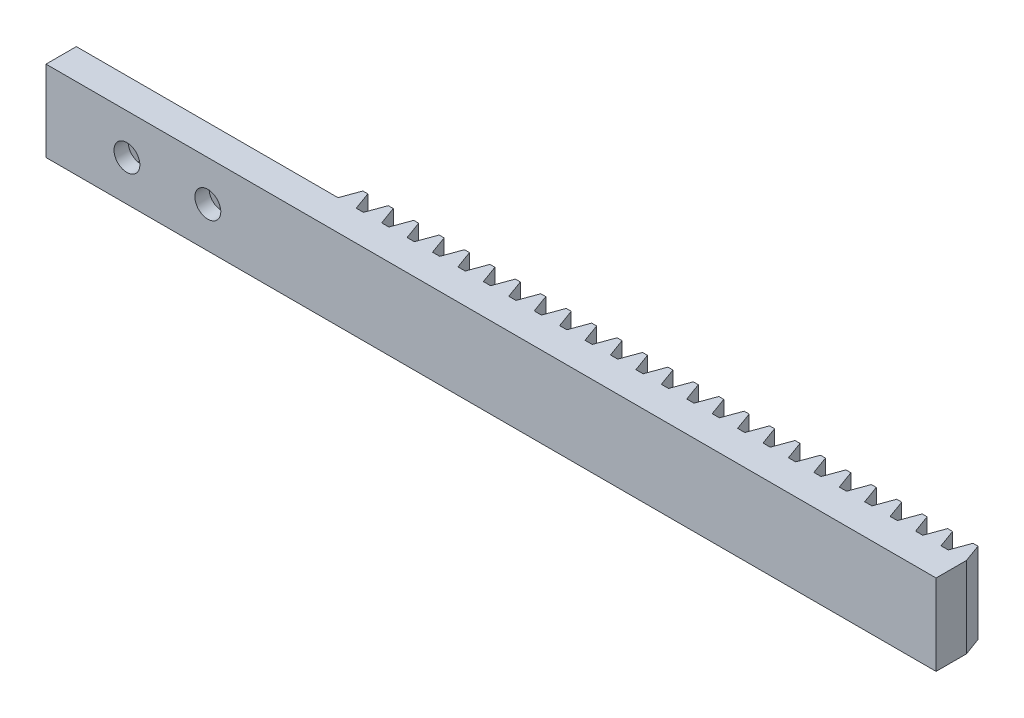
SolidWorks part; units mm, degrees
ref_plane "前视基准面" through (0, 0, 0) normal (0, 0, 1) x (1, 0, 0)
ref_plane "上视基准面" through (0, 0, 0) normal (0, 1, 0) x (1, 0, 0)
ref_plane "右视基准面" through (0, 0, 0) normal (1, 0, 0) x (0, 0, -1)
sketch "草图1" plane through (0, 0, 0) normal (0, 1, 0) x (1, 0, 0)
  line L0 (0, 0) -> (110, 0)
  line L1 (110, 0) -> (110, 3.75)
  line L2 (110, 3.75) -> (109.1812, 5.9996)
  line L3 (109.1812, 5.9996) -> (108.5662, 5.9996)
  line L4 (108.5662, 5.9996) -> (107.7474, 3.75)
  line L6 (0, 3.75) -> (110, 3.75)
  line L103 (0, 3.75) -> (0, 0)
  dimension "D1" = 110
  dimension "D2" = 3.75
  dimension "D3" = 70
  dimension "D4" = 2.394
  dimension "D5" = 0.615
  dimension "D6" = 70
extrude "凸台-拉伸1" add sketch "草图1" along normal blind 10 contours L6 L103 L0 L1 region at (55, 0, -1.875)
extrude "凸台-拉伸2" add sketch "草图1<5>" along normal blind 10 contours L4 L6 L2 L3 region at (108.8737, 0, -4.6607)
sketch "草图1<5>" plane through (0, 0, 0) normal (0, 1, 0) x (1, 0, 0) same geometry as "草图1"
pattern_linear "阵列(线性)1" count 25 spacing 3.142 along (-1, 0, 0) of "凸台-拉伸2"
sketch "草图2" plane through (0, 0, -3.75) normal (0, 0, -1) x (-1, 0, 0)
  line L0 (0, 5) -> (-12.8318, 5) construction
  line L1 (0, 10) -> (0, 0) construction
  circle A0 centre (-10, 5) radius 1.6
  circle A1 centre (-20, 5) radius 1.6
  dimension "D3" = 3.2
  dimension "D4" = 3.2
  dimension "D1" = 10
  dimension "D2" = 10
extrude "切除-拉伸1" cut sketch "草图2" against normal blind 10
sketch "草图3" plane through (0, 0, -3.75) normal (0, 0, -1) x (-1, 0, 0)
  line L1 (-21.5877, 7.75) -> (-23.1754, 5)
  line L2 (-23.1754, 5) -> (-21.5877, 2.25)
  line L3 (-21.5877, 2.25) -> (-18.4123, 2.25)
  line L4 (-18.4123, 2.25) -> (-16.8246, 5)
  line L5 (-16.8246, 5) -> (-18.4123, 7.75)
  line L6 (-18.4123, 7.75) -> (-21.5877, 7.75)
  line L7 (-11.5877, 7.75) -> (-13.1754, 5)
  line L8 (-13.1754, 5) -> (-11.5877, 2.25)
  line L9 (-11.5877, 2.25) -> (-8.4123, 2.25)
  line L10 (-8.4123, 2.25) -> (-6.8246, 5)
  line L11 (-6.8246, 5) -> (-8.4123, 7.75)
  line L12 (-8.4123, 7.75) -> (-11.5877, 7.75)
  circle A0 centre (-20, 5) radius 2.75 construction
  circle A1 centre (-10, 5) radius 2.75 construction
  dimension "D1" = 5.5
  dimension "D2" = 5.5
extrude "切除-拉伸2" cut sketch "草图3" against normal blind 2
